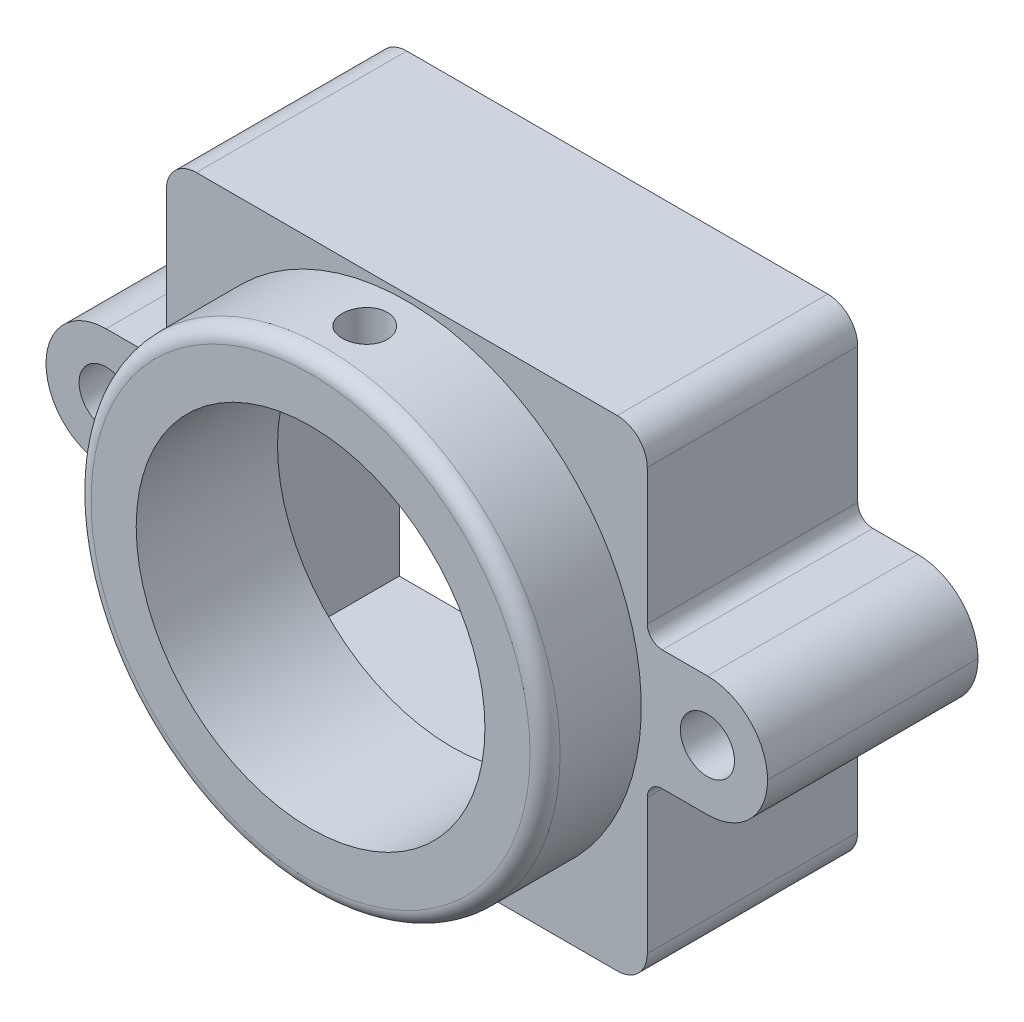
SolidWorks part; units mm, degrees
ref_plane "Front Plane" through (0, 0, 0) normal (0, 0, 1) x (1, 0, 0)
ref_plane "Top Plane" through (0, 0, 0) normal (0, 1, 0) x (1, 0, 0)
ref_plane "Right Plane" through (0, 0, 0) normal (1, 0, 0) x (0, 0, -1)
sketch "Sketch1" plane through (0, 0, 0) normal (0, 0, 1) x (1, 0, 0)
  line L0 (-8, 2) -> (-8, 8)
  line L1 (-8, -8) -> (8, -8)
  line L2 (-8, -8) -> (-8, -2)
  line L3 (-8, 8) -> (8, 8)
  line L4 (8, -8) -> (8, -2)
  line L5 (-8, -8) -> (8, 8) construction
  line L6 (-8, 8) -> (8, -8) construction
  line L7 (12, 2) -> (8, 2)
  line L8 (12, 2) -> (12, -2)
  line L9 (12, -2) -> (8, -2)
  line L10 (-10, 0) -> (10, 0) construction
  line L11 (12, 2) -> (8, -2) construction
  line L12 (12, -2) -> (8, 2) construction
  line L13 (-12, 2) -> (-8, 2)
  line L14 (-12, 2) -> (-12, -2)
  line L15 (-12, -2) -> (-8, -2)
  line L16 (8, 2) -> (8, 8)
  line L17 (-12, 2) -> (-8, -2) construction
  line L18 (-12, -2) -> (-8, 2) construction
  circle A0 centre (10, 0) radius 0.9
  circle A1 centre (-10, 0) radius 0.9
  point P0 (0, 0)
  point P6 (10, 0)
  point P11 (-10, 0)
  point P20 (0, 0)
  dimension "D6" = 1.8
  dimension "D1" = 16
  dimension "D2" = 16
  dimension "D3" = 4
  dimension "D4" = 24
  dimension "D5" = 20
extrude "Boss-Extrude1" add sketch "Sketch1" along normal blind 7
fillet "Fillet1" radius 2 4 edges at (-12, -2, 3.5) (-12, 2, 3.5) (12, -2, 3.5) (12, 2, 3.5)
fillet "Fillet2" radius 1 4 edges at (-8, -8, 3.5) (8, -8, 3.5) (8, 8, 3.5) (-8, 8, 3.5)
fillet "Fillet3" radius 0.5 4 edges at (8, -2, 3.5) (8, 2, 3.5) (-8, -2, 3.5) (-8, 2, 3.5)
sketch "Sketch2" plane through (0, 0, 0) normal (0, 0, -1) x (-1, 0, 0)
  line L1 (-7.25, -7.25) -> (7.25, -7.25)
  line L2 (-7.25, -7.25) -> (-7.25, 7.25)
  line L3 (-7.25, 7.25) -> (7.25, 7.25)
  line L4 (7.25, -7.25) -> (7.25, 7.25)
  line L5 (-7.25, -7.25) -> (7.25, 7.25) construction
  line L6 (-7.25, 7.25) -> (7.25, -7.25) construction
  point P0 (0, 0)
  dimension "D1" = 14.5
  dimension "D2" = 14.5
extrude "Cut-Extrude1" cut sketch "Sketch2" against normal blind 5.5
sketch "Sketch3" plane through (0, 0, 7) normal (0, 0, 1) x (1, 0, 0)
  circle A0 centre (0, 0) radius 7.8
  dimension "D1" = 15.6
extrude "Boss-Extrude2" add sketch "Sketch3" along normal blind 3.2
ref_plane "Plane1" through (0, 0, 0) normal (0, 1, 0) x (1, 0, 0)
sketch "Sketch5" plane through (0, 0, 0) normal (0, 1, 0) x (1, 0, 0)
  line L0 (0, -10.2) -> (0, -7) construction
  line L1 (-7.8, -10.2) -> (7.8, -10.2) construction
  line L2 (-7.8, -7) -> (7.8, -7) construction
  circle A0 centre (0, -8.4) radius 0.75
  dimension "D1" = 1.5
  dimension "D2" = 1.4
extrude "Cut-Extrude2" cut sketch "Sketch5" along normal through all
fillet "Fillet4" radius 0.5 1 edges at (7.8, 0, 10.2)
sketch "Sketch6" plane through (0, 0, 10.2) normal (0, 0, 1) x (1, 0, 0)
  circle A0 centre (0, 0) radius 5.8
  dimension "D1" = 11.6
extrude "Cut-Extrude3" cut sketch "Sketch6" against normal through all
